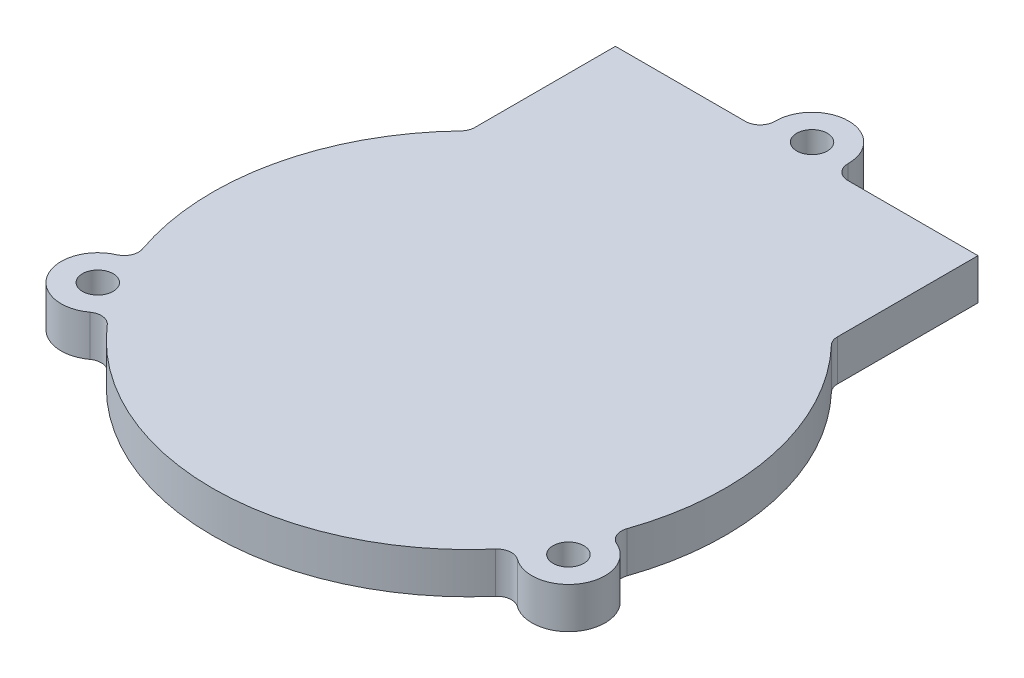
SolidWorks part; units mm, degrees
ref_plane "Front Plane" through (0, 0, 0) normal (0, 0, 1) x (1, 0, 0)
ref_plane "Top Plane" through (0, 0, 0) normal (0, 1, 0) x (1, 0, 0)
ref_plane "Right Plane" through (0, 0, 0) normal (1, 0, 0) x (0, 0, -1)
sketch "Sketch13" plane through (0, 0, 0) normal (0, 1, 0) x (1, 0, 0)
  circle A0 centre (0, 0) radius 35
extrude "Boss-Extrude3" add sketch "Sketch13" along normal blind 5.588
sketch "Sketch14" plane through (0, 5.588, 0) normal (0, 1, 0) x (1, 0, 0)
  line L0 (-24.7478, 24.7497) -> (24.7477, 24.7498)
  line L1 (-24.7478, 24.7497) -> (-24.7479, 44.7452)
  line L2 (24.7477, 24.7498) -> (24.7476, 44.7454)
  line L3 (-24.7479, 44.7452) -> (24.7476, 44.7454)
  line L4 (0, 0) -> (60.4611, -34.8658) construction
  line L5 (0, 0) -> (-56.6044, -32.6614) construction
  line L7 (-3.939, 44.1714) -> (-8.8985, 44.1714)
  line L8 (-3.939, 44.1714) -> (-3.939, 47.547)
  line L9 (-3.939, 47.547) -> (-8.8985, 47.547)
  line L10 (-8.8985, 44.1714) -> (-8.8985, 47.547)
  arc A0 (0, 35) -> (-24.7478, 24.7497) centre (0, 0) ccw construction
  circle A1 centre (0, 0) radius 35 construction
  arc A2 (0, 35) -> (-30.3109, -17.4999) centre (0, 0) ccw construction
  arc A3 (0, 35) -> (30.3118, -17.4984) centre (0, 0) ccw
  arc A4 (0, 35) -> (24.7477, 24.7498) centre (0, 0) ccw construction
  circle A5 centre (32.1365, -18.5413) radius 2.1017
  circle A6 centre (32.1365, -18.5413) radius 4.9951
  circle A7 centre (-32.1465, -18.5162) radius 2.0981
  circle A8 centre (-32.1465, -18.5162) radius 4.9995
extrude "Boss-Extrude4" add sketch "Sketch14" against normal up to surface (5.588 mm away) contours L0 L1 L3 L2 up to face at (0, 0, 35)
sketch "Sketch15" plane through (0, 5.588, 0) normal (0, 1, 0) x (1, 0, 0)
  line L0 (0, 0) -> (0, 62.3966) construction
  line L1 (-0.0001, 44.7453) -> (0, 46.8414) construction
  line L2 (-24.7479, 44.7452) -> (24.7476, 44.7454) construction
  circle A0 centre (0, 46.8414) radius 2.0961
  circle A1 centre (0, 46.8414) radius 4.996
extrude "Boss-Extrude11" add sketch "Sketch15" against normal blind 5.588 contours A1 | A0
extrude "Boss-Extrude12" add sketch "Sketch14<6>" against normal up to surface (5.588 mm away) contours A6 up to face at (0, 0, -29.3038)
sketch "Sketch14<6>" plane through (0, 5.588, 0) normal (0, 1, 0) x (1, 0, 0) same geometry as "Sketch14"
extrude "Boss-Extrude14" add sketch "Sketch14<8>" against normal through all contours L0 A5 region at (32.1365, 5.588, 18.5413)
sketch "Sketch14<8>" plane through (0, 5.588, 0) normal (0, 1, 0) x (1, 0, 0) same geometry as "Sketch14"
hole_wizard "Ø4.2 (4.2) Diameter Hole1" positions "Sketch22" profile "Sketch23" hole size "Ø4.2" standard "ANSI Metric" end condition through all
sketch "Sketch22" plane through (0, 5.588, 0) normal (0, 1, 0) x (1, 0, 0)
  point P0 (32.1248, -18.5356)
sketch "Sketch23" plane through (32.1248, 5.588, 18.5356) normal (1, 0, 0) x (0, 0, 1)
  line L0 (0, 0) -> (0, 5.588)
  line L1 (0, 5.588) -> (2.1, 5.588)
  line L2 (2.1, 5.588) -> (2.1, 0)
  line L5 (2.1, 0) -> (0, 0)
  line L11 (0, -6.35) -> (0, 107.95) construction
  dimension "Thru Hole Dia." = 4.2
  dimension "Thru Hole Depth" = 5.588
extrude "Boss-Extrude15" add sketch "Sketch14<11>" against normal up to surface (5.588 mm away) contours A8 up to face at (32.1248, 0, 20.6356)
sketch "Sketch14<11>" plane through (0, 5.588, 0) normal (0, 1, 0) x (1, 0, 0) same geometry as "Sketch14"
hole_wizard "Ø4.2 (4.2) Diameter Hole2" positions "Sketch26" profile "Sketch27" hole size "Ø4.2" standard "ANSI Metric" end condition through all
sketch "Sketch26" plane through (0, 5.588, 0) normal (0, 1, 0) x (1, 0, 0)
  point P0 (-32.148, -18.5088)
  point P2 (-32.148, -18.5088)
sketch "Sketch27" plane through (-32.148, 5.588, 18.5088) normal (1, 0, 0) x (0, 0, 1)
  line L0 (0, 0) -> (0, 5.588)
  line L1 (0, 5.588) -> (2.1, 5.588)
  line L2 (2.1, 5.588) -> (2.1, 0)
  line L5 (2.1, 0) -> (0, 0)
  line L11 (0, -6.35) -> (0, 107.95) construction
  dimension "Thru Hole Dia." = 4.2
  dimension "Thru Hole Depth" = 5.588
fillet "Fillet4" radius 2 1 edges at (-24.7478, 2.794, -24.7497)
fillet "Fillet6" radius 2 1 edges at (-32.2839, 2.794, 13.5185)
fillet "Fillet7" radius 2 1 edges at (-27.8924, 2.794, 21.1427)
fillet "Fillet8" radius 2 1 edges at (27.8812, 2.794, 21.1574)
fillet "Fillet9" radius 2 1 edges at (32.2715, 2.794, 13.548)
fillet "Fillet10" radius 2 1 edges at (24.7477, 2.794, -24.7498)
fillet "Fillet11" radius 2 1 edges at (4.535, 2.794, -44.7453)
fillet "Fillet12" radius 2 1 edges at (-4.535, 2.794, -44.7453)
